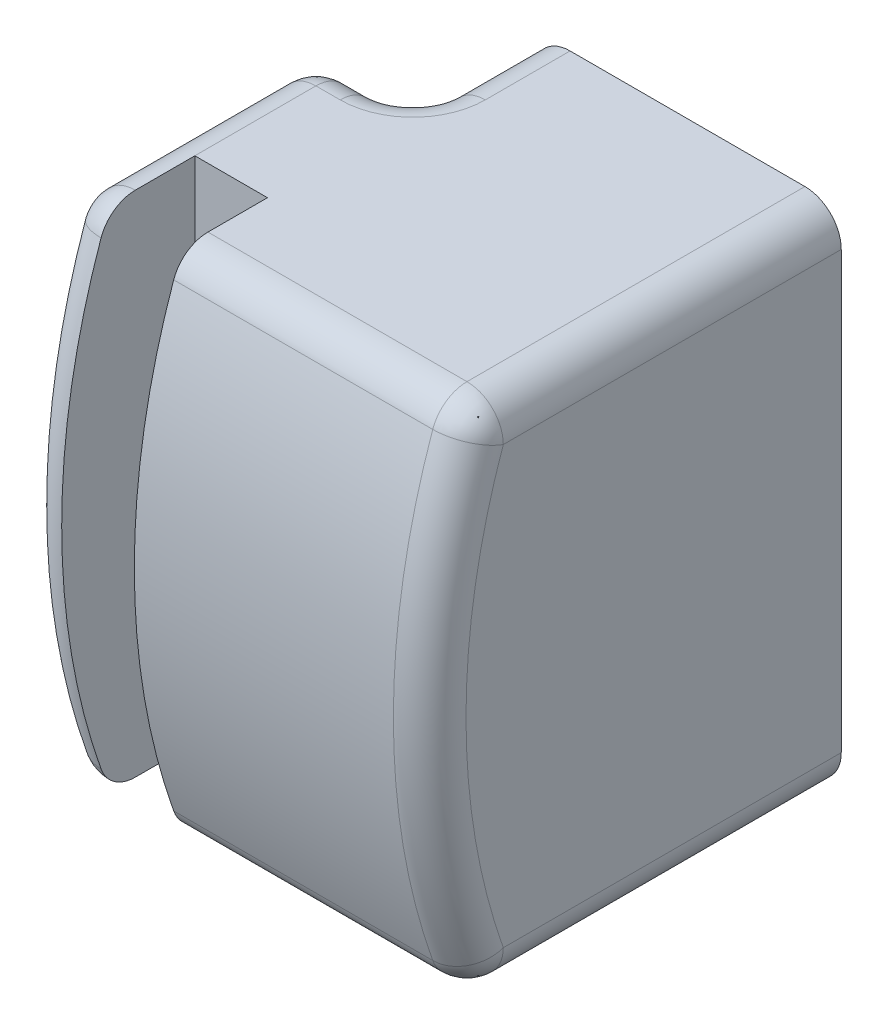
SolidWorks part; units mm, degrees
ref_plane "Alzado" through (0, 0, 0) normal (0, 0, 1) x (1, 0, 0)
ref_plane "Planta" through (0, 0, 0) normal (0, 1, 0) x (1, 0, 0)
ref_plane "Vista lateral" through (0, 0, 0) normal (1, 0, 0) x (0, 0, -1)
sketch "Croquis1" plane through (0, 0, 0) normal (0, 0, 1) x (1, 0, 0)
  line L1 (-58.5, 100) -> (58.5, 100)
  line L2 (-58.5, 100) -> (-58.5, -100)
  line L3 (-58.5, -100) -> (58.5, -100)
  line L4 (58.5, 100) -> (58.5, -100)
  line L5 (-58.5, 100) -> (58.5, -100) construction
  line L6 (-58.5, -100) -> (58.5, 100) construction
  point P0 (0, 0)
  dimension "D1" = 200
  dimension "D2" = 117
extrude "Saliente-Extruir1" add sketch "Croquis1" along normal blind 5
sketch "Croquis2" plane through (0, 0, 5) normal (0, 0, 1) x (1, 0, 0)
  line L1 (-58.5, 100) -> (58.5, 100)
  line L2 (-58.5, 100) -> (-58.5, -100)
  line L3 (-58.5, -100) -> (58.5, -100)
  line L4 (58.5, 100) -> (58.5, -100)
  line L5 (-58.5, 100) -> (58.5, -100) construction
  line L6 (-58.5, -100) -> (58.5, 100) construction
  line L7 (-63.5, 105) -> (63.5, 105)
  line L8 (-63.5, 105) -> (-63.5, -105)
  line L9 (-63.5, -105) -> (63.5, -105)
  line L10 (63.5, 105) -> (63.5, -105)
  line L11 (-63.5, 105) -> (63.5, -105) construction
  line L12 (-63.5, -105) -> (63.5, 105) construction
  point P0 (0, 0)
  point P7 (0, 0)
  dimension "D1" = 5
  dimension "D2" = 5
extrude "Saliente-Extruir2" add sketch "Croquis2" against normal blind 150
sketch "Croquis3" plane through (-63.5, 0, 0) normal (-1, 0, 0) x (0, 0, 1)
  line L0 (5, 105) -> (5, -105)
  line L1 (5, -105) -> (-95, -105)
  line L2 (-145, -105) -> (5, -105) construction
  line L3 (-95, -105) -> (-95, 105)
  line L4 (-145, 105) -> (5, 105) construction
  line L5 (-95, 105) -> (5, 105)
  dimension "D1" = 100
extrude "Saliente-Extruir3" add sketch "Croquis3" along normal blind 40
sketch "Croquis4" plane through (-103.5, 0, 0) normal (-1, 0, 0) x (0, 0, 1)
  line L0 (5, 105) -> (5, -105)
  arc A0 (5, -105) -> (5, 105) centre (-260.625, 0) ccw
  point P2 (25, 0)
  point P6 (5, 0)
  dimension "D1" = 20
extrude "Saliente-Extruir4" add sketch "Croquis4" against normal up to surface (167 mm away) up to face at (63.5, 0, -70)
fillet "Redondeo1" radius 15 14 edges at (63.5, -105, -70) (-63.5, 0, -95) (-63.5, -105, -120) (-83.5, -105, -95) (-63.5, 105, -120) (-83.5, 105, -95) (-103.5, 0, -95) (-103.5, -105, -45) (-20, -105, 5) (-103.5, 0, 25) (-103.5, 105, -45) (63.5, 105, -70) (63.5, 0, 25) (-20, 105, 5)
sketch "Croquis5" plane through (0, 0, 0) normal (0, 0, 1) x (1, 0, 0)
  line L0 (-88.5, 105) -> (-88.5, -105)
  line L1 (-88.5, -105) -> (-58.5, -105)
  line L2 (-58.5, -105) -> (-58.5, 105)
  line L3 (-88.5, 105) -> (48.5, 105) construction
  line L4 (-58.5, 105) -> (-88.5, 105)
  dimension "D1" = 30
extrude "Cortar-Extruir1" cut sketch "Croquis5" against normal blind 30 and the other way through all
sketch "Croquis6" plane through (-58.5, 0, 0) normal (-1, 0, 0) x (0, 0, 1)
  line L0 (-5.4037, -105) -> (-5.4037, -89.5) construction
  line L1 (-5.4037, -89.5) -> (-7.4037, -89.5) construction
  line L2 (-7.4037, -89.5) -> (-7.4037, -40.5) construction
  line L3 (0, -36.1809) -> (-12.5, -36.1809)
  line L4 (0, 100) -> (0, -100) construction
  line L5 (-12.5, -36.1809) -> (-12.5, -44.6528)
  line L6 (-12.5, -44.6528) -> (0, -44.6528)
  line L7 (0, -44.6528) -> (0, -36.1809)
  line L8 (-7.4037, -65) -> (-2.6004, -65) construction
  line L9 (-12.5, -93.8191) -> (-12.5, -85.3472)
  line L10 (0, -93.8191) -> (-12.5, -93.8191)
  line L11 (0, -85.3472) -> (0, -93.8191)
  line L12 (-12.5, -85.3472) -> (0, -85.3472)
  circle A0 centre (-7.4037, -89.5) radius 2.5
  circle A1 centre (-7.4037, -40.5) radius 2.5
  dimension "D3" = 5
  dimension "D1" = 15.5
  dimension "D2" = 2
  dimension "D4" = 49
  dimension "D5" = 12.5
extrude "Saliente-Extruir6" add sketch "Croquis6" against normal blind 2
